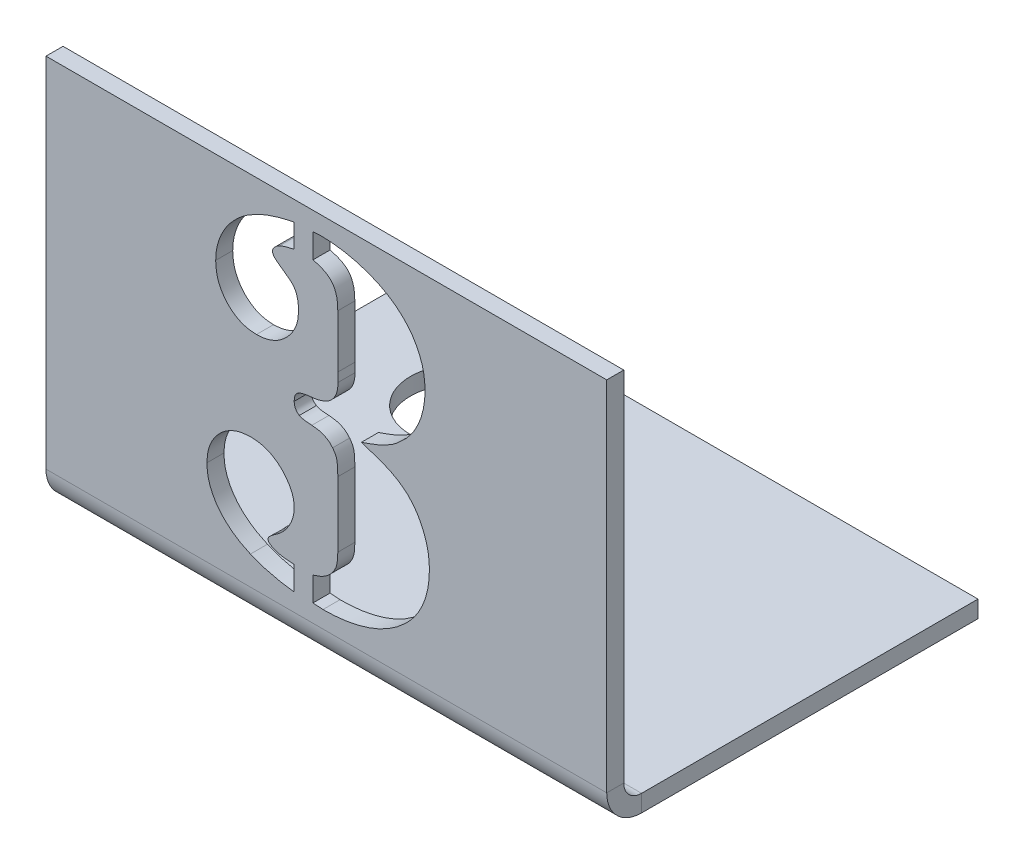
SolidWorks part; units mm, degrees
note: The reader was unsure of these and kept them because the rebuilt part matched: flange length of "Edge-Flange1".
material "16 Ga. SHEET METAL"
ref_plane "Front Plane" through (0, 0, 0) normal (0, 0, 1) x (1, 0, 0)
ref_plane "Top Plane" through (0, 0, 0) normal (0, 1, 0) x (1, 0, 0)
ref_plane "Right Plane" through (0, 0, 0) normal (1, 0, 0) x (0, 0, -1)
sketch "Sketch1" plane through (0, 0, 0) normal (0, 1, 0) x (1, 0, 0)
  line L1 (-25, 0) -> (25, 0)
  line L2 (-25, 0) -> (-25, 30)
  line L3 (-25, 30) -> (25, 30)
  line L4 (25, 0) -> (25, 30)
  dimension "D1" = 30
  dimension "D2" = 50
base flange "Base-Flange1" sketch "Sketch1" thickness 1.5189 reverse thickness direction yes parameters "D1"=1.5875
edge flange "Edge-Flange1" sketch "Sketch8" flange angle 90 flange length 35 flange position bend outside bend radius 1.5875 thickness 1.5189 relief rectangular parameters "D6"=10
sketch "Sketch8" plane through (0, 1.5189, 0) normal (0, 0, 1) x (1, 0, 0)
  line L0 (-25, 0) -> (25, 0) construction
  line L1 (-25, 0) -> (25, 0)
  line L2 (-25, 0) -> (-25, 33.4811)
  line L3 (-25, 33.4811) -> (25, 33.4811)
  line L4 (25, 33.4811) -> (25, 0)
bend "EdgeBend1" bend radius 1.5875 bend angle 90 parameters "D5"=1
hole_wizard "M8 Clearance Hole1" positions "Sketch9" profile "Sketch10" hole size "M8" standard "Peddi DIN" end condition through all
sketch "Sketch9" plane through (0, 1.5189, 0) normal (0, 1, 0) x (1, 0, 0)
  line L0 (25, -3.1064) -> (-25, -3.1064) construction
  line L1 (-25, 30) -> (-25, 0) construction
  point P0 (-13, 21.8936)
  dimension "D1" = 25
  dimension "D2" = 12
sketch "Sketch10" plane through (-13, 1.5189, -21.8936) normal (1, 0, 0) x (0, 0, 1)
  line L0 (0, 0) -> (0, 1.5189)
  line L1 (0, 1.5189) -> (4.5, 1.5189)
  line L2 (4.5, 1.5189) -> (4.5, 0)
  line L5 (4.5, 0) -> (0, 0)
  line L11 (0, -6.35) -> (0, 107.95) construction
  dimension "Thru Hole Dia." = 9
  dimension "Thru Hole Depth" = 1.5189
sketch "Sketch11" plane through (0, 0, 3.1064) normal (0, 0, 1) x (1, 0, 0)
  line L0 (-25, 0) -> (25, 0) construction
  text T0 "3" font "Stencil" height 28
  dimension "D1" = 5
extrude "Cut-Extrude1" cut sketch "Sketch11" against normal through all
other "Freeze***"
sketch "Bend-Lines1" [suppressed] plane through (0, 0, 0) normal (0, 1, 0) x (1, 0, 0)
sketch "Bounding-Box1" [suppressed] plane through (0, 0, 0) normal (0, 1, 0) x (1, 0, 0)
sheet metal parameters "Sheet-Metal1" thickness 1.5189 parameters "D1"=1.5875
flat pattern "Flat-Pattern1" [suppressed]
sketch "Bend-Lines2" plane through (0, 0, 0) normal (0, 1, 0) x (1, 0, 0)
sketch "Bounding-Box2" [suppressed] plane through (0, 0, 0) normal (0, 1, 0) x (1, 0, 0)
sheet metal parameters "Sheet-Metal2" thickness 1.5189 parameters "D1"=1.5875
flat pattern "Flat-Pattern1" [suppressed]
sketch "Bend-Lines2" plane through (0, 0, 0) normal (0, 1, 0) x (1, 0, 0)
sketch "Bounding-Box2" [suppressed] plane through (0, 0, 0) normal (0, 1, 0) x (1, 0, 0)
bend of the flat pattern "Flatten-<EdgeBend1>1"
sheet metal parameters "Sheet-Metal3" thickness 1.5189 parameters "D1"=1.5875
flat pattern "Flat-Pattern1" [suppressed]
sketch "Bend-Lines2" plane through (0, 0, 0) normal (0, 1, 0) x (1, 0, 0)
sketch "Bounding-Box2" [suppressed] plane through (0, 0, 0) normal (0, 1, 0) x (1, 0, 0)
bend of the flat pattern "Flatten-<EdgeBend1>1"
sheet metal parameters "Sheet-Metal4" thickness 1.5189 parameters "D1"=1.5875
flat pattern "Flat-Pattern1"
sketch "Bend-Lines2" plane through (0, 0, 0) normal (0, -1, 0) x (-1, 0, 0)
  line L0 (-25, -1.724) -> (25, -1.724) construction
  line L1 (-25, -1.724) -> (25, -1.724) construction
sketch3d "Bounding-Box2" [suppressed]
  line L0 (25, -35.3416, 0) -> (25, 30, 0) construction
  line L1 (-25, -35.3416, 0) -> (-25, 30, 0) construction
  line L2 (25, -35.3416, 0) -> (-25, -35.3416, 0) construction
  line L3 (25, 30, 0) -> (-25, 30, 0) construction
bend of the flat pattern "Flatten-<EdgeBend1>1"
